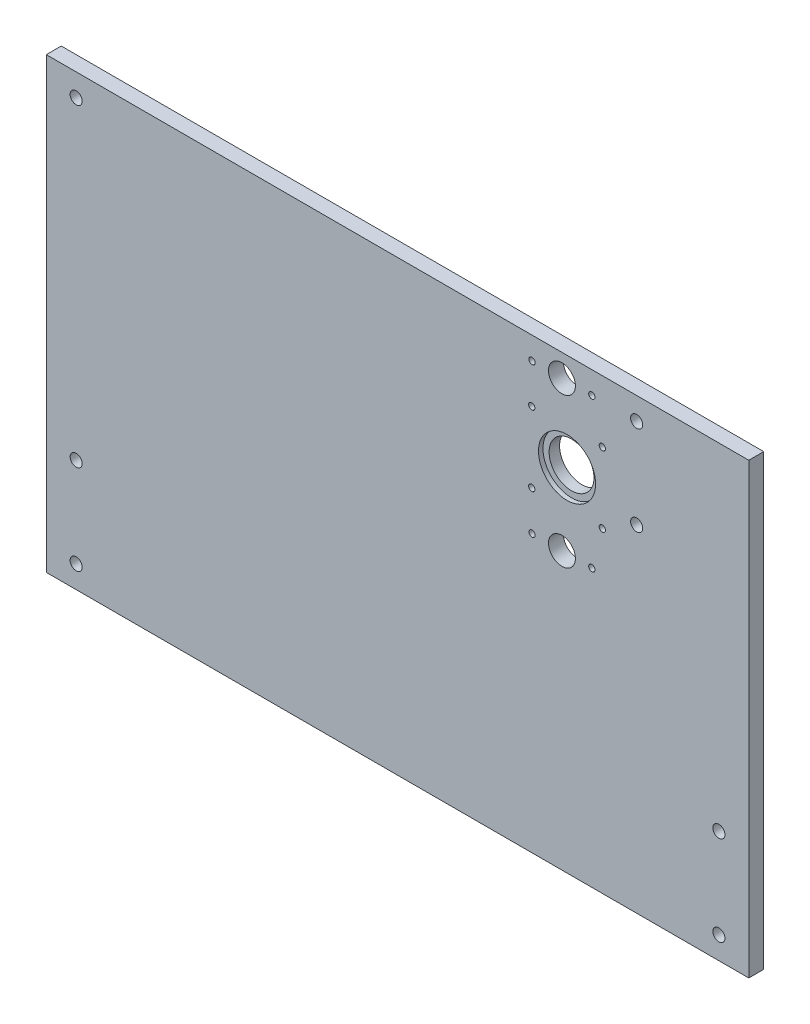
SolidWorks part; units mm, degrees
material "6061 Alloy"
ref_plane "Front Plane" through (0, 0, 0) normal (0, 0, 1) x (1, 0, 0)
ref_plane "Top Plane" through (0, 0, 0) normal (0, 1, 0) x (1, 0, 0)
ref_plane "Right Plane" through (0, 0, 0) normal (1, 0, 0) x (0, 0, -1)
sketch "Sketch2" plane through (0, 0, 0) normal (0, 0, 1) x (1, 0, 0)
  line L1 (-235, -150) -> (235, -150)
  line L2 (-235, -150) -> (-235, 150)
  line L3 (-235, 150) -> (235, 150)
  line L4 (235, -150) -> (235, 150)
  line L5 (-235, -150) -> (235, 150) construction
  line L6 (-235, 150) -> (235, -150) construction
  point P0 (0, 0)
  dimension "D1" = 470
  dimension "D2" = 300
extrude "Boss-Extrude1" add sketch "Sketch2" along normal mid plane 10
sketch "Sketch3" plane through (0, 0, 5) normal (0, 0, 1) x (1, 0, 0)
  line L0 (-215, -1058.5557) -> (-215, 48941.4443) construction
  line L1 (-235, 150) -> (-235, -150) construction
  line L2 (-1130.8828, -135) -> (48869.1172, -135) construction
  line L3 (-1138.1256, -75) -> (48861.8744, -75) construction
  line L4 (-235, -150) -> (235, -150) construction
  line L5 (215, -1025.1068) -> (215, 48974.8932) construction
  line L6 (235, -150) -> (235, 150) construction
  circle A0 centre (-215, -75) radius 4.05
  circle A1 centre (-215, -135) radius 4.05
  circle A2 centre (215, -75) radius 4.05
  circle A3 centre (215, -135) radius 4.05
  dimension "D5" = 8.1
  dimension "D6" = 8.1
  dimension "D7" = 8.1
  dimension "D8" = 8.1
  dimension "D1" = 20
  dimension "D2" = 15
  dimension "D3" = 60
  dimension "D4" = 20
extrude "Cut-Extrude1" cut sketch "Sketch3" against normal blind 10
sketch "Sketch4" plane through (0, 0, 5) normal (0, 0, 1) x (1, 0, 0)
  line L0 (-1048.1305, 135) -> (48951.8695, 135) construction
  line L1 (-1078.5537, 35) -> (48921.4463, 35) construction
  line L2 (110, -948.1906) -> (110, 49051.8094) construction
  line L3 (-235, -150) -> (235, -150) construction
  line L4 (-235, 150) -> (-235, -150) construction
  circle A0 centre (110, 135) radius 9
  circle A1 centre (110, 35) radius 9
  circle A2 centre (90, 135) radius 2.1
  circle A3 centre (130, 135) radius 2.1
  circle A4 centre (130, 35) radius 2.1
  circle A5 centre (90, 35) radius 2.1
  dimension "D4" = 18
  dimension "D5" = 18
  dimension "D8" = 4.2
  dimension "D9" = 4.2
  dimension "D12" = 4.2
  dimension "D13" = 4.2
  dimension "D1" = 185
  dimension "D2" = 100
  dimension "D3" = 345
  dimension "D6" = 20
  dimension "D7" = 20
  dimension "D10" = 20
  dimension "D11" = 20
extrude "Cut-Extrude2" cut sketch "Sketch4" against normal through all
sketch "Sketch5" plane through (0, 0, 5) normal (0, 0, 1) x (1, 0, 0)
  line L0 (160, -981.5111) -> (160, 49018.4889) construction
  line L1 (-1025.0374, 135) -> (48974.9626, 135) construction
  line L2 (-1021.6922, 75) -> (48978.3078, 75) construction
  line L3 (235, 150) -> (-235, 150) construction
  circle A0 centre (110, 135) radius 9 construction
  circle A1 centre (160, 135) radius 4.05
  circle A2 centre (160, 75) radius 4.05
  dimension "D1" = 50
  dimension "D4" = 8.1
  dimension "D5" = 8.1
  dimension "D2" = 15
  dimension "D3" = 60
extrude "Cut-Extrude3" cut sketch "Sketch5" against normal through all
sketch "Sketch6" plane through (0, 0, 5) normal (0, 0, 1) x (1, 0, 0)
  line L0 (-235, 150) -> (-235, -150) construction
  line L1 (235, 150) -> (-235, 150) construction
  circle A0 centre (-215, 135) radius 4.05
  dimension "D3" = 8.1
  dimension "D1" = 20
  dimension "D2" = 15
extrude "Cut-Extrude4" cut sketch "Sketch6" against normal through all
sketch "Sketch7" plane through (0, 0, 5) normal (0, 0, 1) x (1, 0, 0)
  circle A0 centre (113.4, 85) radius 19.1
  circle A1 centre (110, 135) radius 9 construction
  dimension "D1" = 38.2
  dimension "D2" = 3.4
  dimension "D3" = 50
extrude "Cut-Extrude5" cut sketch "Sketch7" against normal blind 3
sketch "Sketch8" plane through (0, 0, 2) normal (0, 0, 1) x (1, 0, 0)
  circle A0 centre (113.4, 85) radius 15
  dimension "D1" = 30
extrude "Cut-Extrude6" cut sketch "Sketch8" against normal through all
sketch "Sketch9" plane through (0, 0, 5) normal (0, 0, 1) x (1, 0, 0)
  line L1 (89.8, 61.4) -> (137, 61.4) construction
  line L2 (89.8, 61.4) -> (89.8, 108.6) construction
  line L3 (89.8, 108.6) -> (137, 108.6) construction
  line L4 (137, 61.4) -> (137, 108.6) construction
  line L5 (89.8, 61.4) -> (137, 108.6) construction
  line L6 (89.8, 108.6) -> (137, 61.4) construction
  circle A0 centre (89.8, 108.6) radius 2.1
  circle A1 centre (137, 108.6) radius 2.1
  circle A2 centre (137, 61.4) radius 2.1
  circle A3 centre (89.8, 61.4) radius 2.1
  point P0 (113.4, 85)
  dimension "D3" = 4.2
  dimension "D4" = 4.2
  dimension "D5" = 4.2
  dimension "D6" = 4.2
  dimension "D1" = 47.2
  dimension "D2" = 47.2
extrude "Cut-Extrude7" cut sketch "Sketch9" against normal through all
equation "\"D6@Sketch3\"=\"D5@Sketch3\""
equation "\"D7@Sketch3\"=\"D5@Sketch3\""
equation "\"D8@Sketch3\"=\"D5@Sketch3\""
equation "\"D5@Sketch4\"=\"D4@Sketch4\""
equation "\"D1@Sketch5\"=35+15"
equation "\"D4@Sketch9\"=\"D3@Sketch9\""
equation "\"D5@Sketch9\"=\"D3@Sketch9\""
equation "\"D6@Sketch9\"=\"D3@Sketch9\""
